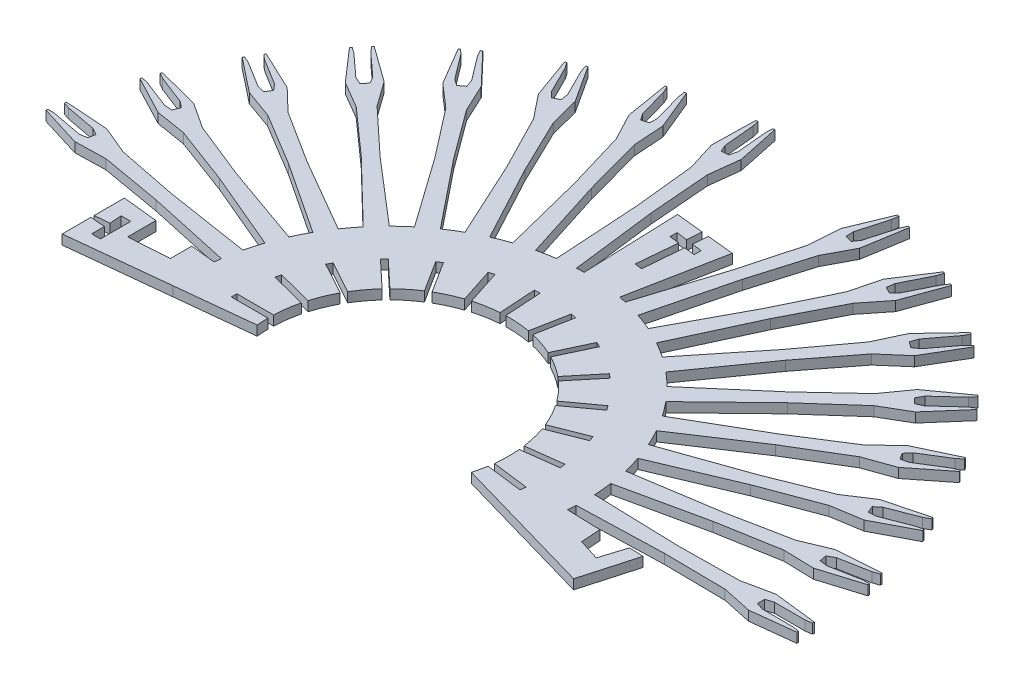
SolidWorks part; units mm, degrees
ref_plane "Front Plane" through (0, 0, 0) normal (0, 0, 1) x (1, 0, 0)
ref_plane "Top Plane" through (0, 0, 0) normal (0, 1, 0) x (1, 0, 0)
ref_plane "Right Plane" through (0, 0, 0) normal (1, 0, 0) x (0, 0, -1)
sketch "Sketch1" plane through (0, 0, 0) normal (0, 1, 0) x (1, 0, 0)
  line L5558 (72.849, 49.9) -> (72.743, 47.748) construction
  line L5559 (72.743, 47.748) -> (72.425, 45.667) construction
  line L5560 (72.425, 45.667) -> (71.896, 43.656) construction
  line L5561 (71.896, 43.656) -> (71.208, 41.716) construction
  line L5562 (71.208, 41.716) -> (70.309, 39.899) construction
  line L5563 (70.309, 39.899) -> (69.286, 38.171) construction
  line L5564 (69.286, 38.171) -> (66.71, 35.048) construction
  line L5565 (66.71, 35.048) -> (63.588, 32.491) construction
  line L5566 (63.588, 32.491) -> (61.877, 31.45) construction
  line L5567 (61.877, 31.45) -> (60.043, 30.551) construction
  line L5568 (60.043, 30.551) -> (58.12, 29.863) construction
  line L5569 (58.12, 29.863) -> (56.109, 29.333) construction
  line L5570 (56.109, 29.333) -> (54.01, 29.016) construction
  line L5571 (54.01, 29.016) -> (51.876, 28.91) construction
  line L5572 (51.876, 28.91) -> (49.724, 29.016) construction
  line L5573 (49.724, 29.016) -> (47.643, 29.333) construction
  line L5574 (47.643, 29.333) -> (45.632, 29.863) construction
  line L5575 (45.632, 29.863) -> (43.692, 30.551) construction
  line L5576 (43.692, 30.551) -> (41.839, 31.45) construction
  line L5577 (41.839, 31.45) -> (40.128, 32.491) construction
  line L5578 (40.128, 32.491) -> (37.006, 35.048) construction
  line L5579 (37.006, 35.048) -> (34.431, 38.171) construction
  line L5580 (34.431, 38.171) -> (33.408, 39.899) construction
  line L5581 (33.408, 39.899) -> (32.508, 41.716) construction
  line L5582 (32.508, 41.716) -> (31.821, 43.656) construction
  line L5583 (31.821, 43.656) -> (31.291, 45.667) construction
  line L5584 (31.291, 45.667) -> (30.974, 47.748) construction
  line L5585 (30.974, 47.748) -> (30.868, 49.9) construction
  line L5586 (30.868, 49.9) -> (30.974, 52.035) construction
  line L5587 (30.974, 52.035) -> (31.291, 54.134) construction
  line L5588 (31.291, 54.134) -> (31.821, 56.145) construction
  line L5589 (31.821, 56.145) -> (32.508, 58.067) construction
  line L5590 (32.508, 58.067) -> (33.408, 59.919) construction
  line L5591 (33.408, 59.919) -> (34.431, 61.648) construction
  line L5592 (34.431, 61.648) -> (37.006, 64.77) construction
  line L5593 (37.006, 64.77) -> (40.128, 67.328) construction
  line L5594 (40.128, 67.328) -> (41.839, 68.368) construction
  line L5595 (41.839, 68.368) -> (43.692, 69.268) construction
  line L5596 (43.692, 69.268) -> (45.632, 69.956) construction
  line L5597 (45.632, 69.956) -> (47.643, 70.485) construction
  line L5598 (47.643, 70.485) -> (49.724, 70.803) construction
  line L5599 (49.724, 70.803) -> (51.876, 70.908) construction
  line L5600 (51.876, 70.908) -> (54.01, 70.803) construction
  line L5601 (54.01, 70.803) -> (56.109, 70.485) construction
  line L5602 (56.109, 70.485) -> (58.12, 69.956) construction
  line L5603 (58.12, 69.956) -> (60.043, 69.268) construction
  line L5604 (60.043, 69.268) -> (61.877, 68.368) construction
  line L5605 (61.877, 68.368) -> (63.588, 67.328) construction
  line L5606 (63.588, 67.328) -> (66.71, 64.77) construction
  line L5607 (66.71, 64.77) -> (69.286, 61.648) construction
  line L5608 (69.286, 61.648) -> (70.309, 59.919) construction
  line L5609 (70.309, 59.919) -> (71.208, 58.067) construction
  line L5610 (71.208, 58.067) -> (71.896, 56.145) construction
  line L5611 (71.896, 56.145) -> (72.425, 54.134) construction
  line L5612 (72.425, 54.134) -> (72.743, 52.035) construction
  line L5613 (72.743, 52.035) -> (72.849, 49.9) construction
  line L5614 (62.054, 49.9) -> (61.842, 47.854) construction
  line L5615 (61.842, 47.854) -> (61.26, 45.932) construction
  line L5616 (61.26, 45.932) -> (60.307, 44.203) construction
  line L5617 (60.307, 44.203) -> (59.055, 42.704) construction
  line L5618 (59.055, 42.704) -> (57.556, 41.451) construction
  line L5619 (57.556, 41.451) -> (55.827, 40.499) construction
  line L5620 (55.827, 40.499) -> (53.922, 39.917) construction
  line L5621 (53.922, 39.917) -> (51.858, 39.705) construction
  line L5622 (51.858, 39.705) -> (49.795, 39.917) construction
  line L5623 (49.795, 39.917) -> (47.89, 40.499) construction
  line L5624 (47.89, 40.499) -> (46.143, 41.451) construction
  line L5625 (46.143, 41.451) -> (44.644, 42.704) construction
  line L5626 (44.644, 42.704) -> (43.392, 44.203) construction
  line L5627 (43.392, 44.203) -> (42.439, 45.932) construction
  line L5628 (42.439, 45.932) -> (41.857, 47.854) construction
  line L5629 (41.857, 47.854) -> (41.645, 49.9) construction
  line L5630 (41.645, 49.9) -> (41.857, 51.964) construction
  line L5631 (41.857, 51.964) -> (42.439, 53.869) construction
  line L5632 (42.439, 53.869) -> (43.392, 55.615) construction
  line L5633 (43.392, 55.615) -> (44.644, 57.115) construction
  line L5634 (44.644, 57.115) -> (46.143, 58.367) construction
  line L5635 (46.143, 58.367) -> (47.89, 59.32) construction
  line L5636 (47.89, 59.32) -> (49.795, 59.902) construction
  line L5637 (49.795, 59.902) -> (51.858, 60.113) construction
  line L5638 (51.858, 60.113) -> (53.922, 59.902) construction
  line L5639 (53.922, 59.902) -> (55.827, 59.32) construction
  line L5640 (55.827, 59.32) -> (57.556, 58.367) construction
  line L5641 (57.556, 58.367) -> (59.055, 57.115) construction
  line L5642 (59.055, 57.115) -> (60.307, 55.615) construction
  line L5643 (60.307, 55.615) -> (61.26, 53.869) construction
  line L5644 (61.26, 53.869) -> (61.842, 51.964) construction
  line L5645 (61.842, 51.964) -> (62.054, 49.9) construction
  line L5646 (30.85, 49.9) -> (51.841, 49.9) construction
  line L5647 (53.675, 70.82) -> (51.841, 49.9) construction
  line L5648 (72.531, 46.249) -> (51.858, 49.9) construction
  line L5649 (72.796, 48.436) -> (51.841, 49.9) construction
  line L5650 (51.488, 70.891) -> (51.841, 49.9) construction
  line L5651 (55.862, 70.52) -> (51.858, 49.9) construction
  line L5652 (30.956, 47.696) -> (51.841, 49.9) construction
  line L5653 (30.956, 52.088) -> (51.841, 49.9) construction
  line L5654 (72.037, 44.115) -> (51.841, 49.9) construction
  line L5655 (62.406, 49.177) -> (67.045, 49.424) construction
  line L5656 (67.345, 50.077) -> (67.469, 50.324) construction
  line L5657 (67.469, 50.324) -> (67.68, 50.377) construction
  line L5658 (67.68, 50.377) -> (67.892, 50.271) construction
  line L5659 (67.892, 50.271) -> (67.945, 50.059) construction
  line L5660 (67.945, 50.059) -> (67.839, 49.848) construction
  line L5661 (67.839, 49.848) -> (67.628, 49.759) construction
  line L5662 (67.628, 49.759) -> (67.416, 49.865) construction
  line L5663 (67.416, 49.865) -> (67.345, 50.077) construction
  line L5664 (69.832, 50.094) -> (69.938, 50.341) construction
  line L5665 (69.938, 50.341) -> (70.168, 50.394) construction
  line L5666 (70.168, 50.394) -> (70.379, 50.288) construction
  line L5667 (70.379, 50.288) -> (70.432, 50.077) construction
  line L5668 (70.432, 50.077) -> (70.326, 49.865) construction
  line L5669 (70.326, 49.865) -> (70.115, 49.777) construction
  line L5670 (70.115, 49.777) -> (69.903, 49.883) construction
  line L5671 (69.903, 49.883) -> (69.832, 50.094) construction
  line L5672 (67.045, 49.424) -> (71.702, 49.477) construction
  line L5673 (71.914, 50.094) -> (71.702, 49.477) construction
  line L5674 (62.389, 50.835) -> (67.045, 50.659) construction
  line L5675 (67.045, 50.659) -> (71.702, 50.712) construction
  line L5676 (71.914, 50.094) -> (71.702, 50.712) construction
  line L5677 (70.132, 50.377) -> (67.645, 50.359) construction
  line L5678 (70.15, 49.777) -> (67.645, 49.742) construction
  line L5679 (57.344, 49.953) -> (51.841, 49.9) construction
  line L5680 (62.353, 51.118) -> (66.887, 52.229) construction
  line L5681 (67.045, 52.917) -> (67.345, 53.252) construction
  line L5682 (67.345, 53.252) -> (67.557, 53.199) construction
  line L5683 (67.557, 53.199) -> (67.663, 52.987) construction
  line L5684 (67.663, 52.987) -> (67.61, 52.776) construction
  line L5685 (67.61, 52.776) -> (67.398, 52.652) construction
  line L5686 (67.398, 52.652) -> (67.187, 52.723) construction
  line L5687 (67.187, 52.723) -> (67.045, 52.917) construction
  line L5688 (69.48, 53.393) -> (69.779, 53.746) construction
  line L5689 (69.779, 53.746) -> (69.991, 53.693) construction
  line L5690 (69.991, 53.693) -> (70.097, 53.481) construction
  line L5691 (70.097, 53.481) -> (70.044, 53.269) construction
  line L5692 (70.044, 53.269) -> (69.832, 53.128) construction
  line L5693 (69.832, 53.128) -> (69.621, 53.217) construction
  line L5694 (69.621, 53.217) -> (69.48, 53.393) construction
  line L5695 (66.887, 52.229) -> (71.455, 53.128) construction
  line L5696 (71.543, 53.763) -> (71.455, 53.128) construction
  line L5697 (62.036, 52.758) -> (66.64, 53.428) construction
  line L5698 (66.64, 53.428) -> (71.208, 54.328) construction
  line L5699 (71.543, 53.781) -> (71.208, 54.328) construction
  line L5700 (69.744, 53.728) -> (67.292, 53.252) construction
  line L5701 (69.85, 53.128) -> (67.416, 52.634) construction
  line L5702 (57.238, 50.959) -> (51.841, 49.9) construction
  line L5703 (61.965, 53.023) -> (66.199, 54.945) construction
  line L5704 (66.234, 55.651) -> (66.446, 56.039) construction
  line L5705 (66.446, 56.039) -> (66.693, 56.021) construction
  line L5706 (66.693, 56.021) -> (66.851, 55.827) construction
  line L5707 (66.851, 55.827) -> (66.64, 55.457) construction
  line L5708 (66.64, 55.457) -> (66.393, 55.492) construction
  line L5709 (66.393, 55.492) -> (66.234, 55.651) construction
  line L5710 (68.545, 56.568) -> (68.756, 56.956) construction
  line L5711 (68.756, 56.956) -> (69.003, 56.938) construction
  line L5712 (69.003, 56.938) -> (69.162, 56.744) construction
  line L5713 (69.162, 56.744) -> (68.95, 56.374) construction
  line L5714 (68.95, 56.374) -> (68.703, 56.409) construction
  line L5715 (68.703, 56.409) -> (68.545, 56.568) construction
  line L5716 (66.199, 54.945) -> (70.52, 56.656) construction
  line L5717 (70.503, 57.309) -> (70.52, 56.656) construction
  line L5718 (61.348, 54.575) -> (65.74, 56.092) construction
  line L5719 (65.74, 56.092) -> (70.079, 57.803) construction
  line L5720 (70.503, 57.309) -> (70.079, 57.803) construction
  line L5721 (68.739, 56.938) -> (66.41, 56.021) construction
  line L5722 (68.968, 56.374) -> (66.64, 55.439) construction
  line L5723 (56.956, 51.929) -> (51.841, 49.9) construction
  line L5724 (61.225, 54.822) -> (65.035, 57.485) construction
  line L5725 (64.946, 58.191) -> (65.07, 58.614) construction
  line L5726 (65.07, 58.614) -> (65.317, 58.632) construction
  line L5727 (65.317, 58.632) -> (65.493, 58.473) construction
  line L5728 (65.493, 58.473) -> (65.528, 58.244) construction
  line L5729 (65.528, 58.244) -> (65.37, 58.05) construction
  line L5730 (65.37, 58.05) -> (64.946, 58.191) construction
  line L5731 (67.045, 59.514) -> (67.169, 59.937) construction
  line L5732 (67.169, 59.937) -> (67.416, 59.955) construction
  line L5733 (67.416, 59.955) -> (67.592, 59.796) construction
  line L5734 (67.592, 59.796) -> (67.628, 59.567) construction
  line L5735 (67.628, 59.567) -> (67.469, 59.373) construction
  line L5736 (67.469, 59.373) -> (67.045, 59.514) construction
  line L5737 (65.035, 57.485) -> (68.968, 59.972) construction
  line L5738 (68.827, 60.607) -> (68.968, 59.972) construction
  line L5739 (60.325, 56.233) -> (64.382, 58.526) construction
  line L5740 (64.382, 58.526) -> (68.315, 61.013) construction
  line L5741 (68.827, 60.607) -> (68.315, 61.013) construction
  line L5742 (67.169, 59.919) -> (65.052, 58.579) construction
  line L5743 (67.486, 59.39) -> (65.37, 58.067) construction
  line L5744 (56.497, 52.828) -> (51.858, 49.9) construction
  line L5745 (60.149, 56.444) -> (63.429, 59.761) construction
  line L5746 (63.2, 60.448) -> (63.147, 60.678) construction
  line L5747 (63.147, 60.678) -> (63.288, 60.889) construction
  line L5748 (63.288, 60.889) -> (63.5, 60.942) construction
  line L5749 (63.5, 60.942) -> (63.712, 60.837) construction
  line L5750 (63.712, 60.837) -> (63.765, 60.607) construction
  line L5751 (63.765, 60.607) -> (63.659, 60.396) construction
  line L5752 (63.659, 60.396) -> (63.412, 60.343) construction
  line L5753 (63.412, 60.343) -> (63.2, 60.448) construction
  line L5754 (65.017, 62.124) -> (64.964, 62.371) construction
  line L5755 (64.964, 62.371) -> (65.105, 62.583) construction
  line L5756 (65.105, 62.583) -> (65.317, 62.636) construction
  line L5757 (65.317, 62.636) -> (65.528, 62.53) construction
  line L5758 (65.528, 62.53) -> (65.581, 62.283) construction
  line L5759 (65.581, 62.283) -> (65.476, 62.071) construction
  line L5760 (65.476, 62.071) -> (65.229, 62.018) construction
  line L5761 (65.229, 62.018) -> (65.017, 62.124) construction
  line L5762 (63.429, 59.761) -> (66.834, 62.936) construction
  line L5763 (66.587, 63.535) -> (66.834, 62.936) construction
  line L5764 (59.02, 57.679) -> (62.583, 60.678) construction
  line L5765 (62.583, 60.678) -> (66.005, 63.835) construction
  line L5766 (66.587, 63.535) -> (66.005, 63.835) construction
  line L5767 (65.07, 62.548) -> (63.235, 60.854) construction
  line L5768 (65.493, 62.089) -> (63.659, 60.396) construction
  line L5769 (55.88, 53.622) -> (51.841, 49.9) construction
  line L5770 (58.808, 57.873) -> (61.419, 61.718) construction
  line L5771 (61.083, 62.353) -> (60.995, 62.583) construction
  line L5772 (60.995, 62.583) -> (61.083, 62.794) construction
  line L5773 (61.083, 62.794) -> (61.295, 62.9) construction
  line L5774 (61.295, 62.9) -> (61.507, 62.83) construction
  line L5775 (61.507, 62.83) -> (61.613, 62.618) construction
  line L5776 (61.613, 62.618) -> (61.524, 62.371) construction
  line L5777 (61.524, 62.371) -> (61.313, 62.301) construction
  line L5778 (61.313, 62.301) -> (61.083, 62.353) construction
  line L5779 (62.565, 64.329) -> (62.477, 64.576) construction
  line L5780 (62.477, 64.576) -> (62.565, 64.788) construction
  line L5781 (62.565, 64.788) -> (62.777, 64.893) construction
  line L5782 (62.777, 64.893) -> (62.988, 64.805) construction
  line L5783 (62.988, 64.805) -> (63.094, 64.594) construction
  line L5784 (63.094, 64.594) -> (63.006, 64.364) construction
  line L5785 (63.006, 64.364) -> (62.794, 64.276) construction
  line L5786 (62.794, 64.276) -> (62.565, 64.329) construction
  line L5787 (61.419, 61.718) -> (64.206, 65.458) construction
  line L5788 (63.835, 66.005) -> (64.206, 65.458) construction
  line L5789 (57.485, 58.861) -> (60.431, 62.459) construction
  line L5790 (60.431, 62.459) -> (63.2, 66.199) construction
  line L5791 (63.835, 66.005) -> (63.2, 66.199) construction
  line L5792 (62.53, 64.752) -> (61.031, 62.759) construction
  line L5793 (63.024, 64.382) -> (61.524, 62.389) construction
  line L5794 (55.122, 54.31) -> (51.858, 49.9) construction
  line L5795 (57.238, 59.002) -> (59.09, 63.271) construction
  line L5796 (58.649, 63.835) -> (58.508, 64.047) construction
  line L5797 (58.508, 64.047) -> (58.561, 64.258) construction
  line L5798 (58.561, 64.258) -> (58.755, 64.417) construction
  line L5799 (58.755, 64.417) -> (58.967, 64.364) construction
  line L5800 (58.967, 64.364) -> (59.126, 64.17) construction
  line L5801 (59.126, 64.17) -> (59.073, 63.941) construction
  line L5802 (59.073, 63.941) -> (58.879, 63.8) construction
  line L5803 (58.879, 63.8) -> (58.649, 63.835) construction
  line L5804 (59.743, 66.058) -> (59.602, 66.269) construction
  line L5805 (59.602, 66.269) -> (59.655, 66.481) construction
  line L5806 (59.655, 66.481) -> (59.849, 66.604) construction
  line L5807 (59.849, 66.604) -> (60.06, 66.587) construction
  line L5808 (60.06, 66.587) -> (60.219, 66.393) construction
  line L5809 (60.219, 66.393) -> (60.166, 66.163) construction
  line L5810 (60.166, 66.163) -> (59.972, 66.022) construction
  line L5811 (59.972, 66.022) -> (59.743, 66.058) construction
  line L5812 (59.09, 63.271) -> (61.136, 67.451) construction
  line L5813 (60.695, 67.927) -> (61.136, 67.451) construction
  line L5814 (55.739, 59.743) -> (57.979, 63.818) construction
  line L5815 (57.979, 63.818) -> (60.025, 67.998) construction
  line L5816 (60.678, 67.927) -> (60.025, 67.998) construction
  line L5817 (59.619, 66.463) -> (58.526, 64.223) construction
  line L5818 (60.184, 66.181) -> (59.073, 63.941) construction
  line L5819 (54.257, 54.822) -> (51.841, 49.9) construction
  line L5820 (55.457, 59.849) -> (56.497, 64.382) construction
  line L5821 (55.951, 64.841) -> (55.792, 64.999) construction
  line L5822 (55.792, 64.999) -> (55.792, 65.246) construction
  line L5823 (55.792, 65.246) -> (55.951, 65.423) construction
  line L5824 (55.951, 65.423) -> (56.18, 65.423) construction
  line L5825 (56.18, 65.423) -> (56.339, 65.264) construction
  line L5826 (56.339, 65.264) -> (56.339, 65.035) construction
  line L5827 (56.339, 65.035) -> (56.18, 64.876) construction
  line L5828 (56.18, 64.876) -> (55.951, 64.841) construction
  line L5829 (56.603, 67.239) -> (56.444, 67.398) construction
  line L5830 (56.444, 67.398) -> (56.444, 67.628) construction
  line L5831 (56.444, 67.628) -> (56.603, 67.822) construction
  line L5832 (56.603, 67.822) -> (56.85, 67.822) construction
  line L5833 (56.85, 67.822) -> (57.009, 67.663) construction
  line L5834 (57.009, 67.663) -> (57.009, 67.416) construction
  line L5835 (57.009, 67.416) -> (56.85, 67.257) construction
  line L5836 (56.85, 67.257) -> (56.603, 67.239) construction
  line L5837 (56.497, 64.382) -> (57.732, 68.88) construction
  line L5838 (57.203, 69.25) -> (57.732, 68.88) construction
  line L5839 (53.852, 60.29) -> (55.298, 64.717) construction
  line L5840 (55.298, 64.717) -> (56.533, 69.197) construction
  line L5841 (57.185, 69.25) -> (56.533, 69.197) construction
  line L5842 (56.427, 67.61) -> (55.757, 65.211) construction
  line L5843 (57.009, 67.451) -> (56.356, 65.035) construction
  line L5844 (53.305, 55.192) -> (51.841, 49.9) construction
  line L5845 (51.664, 60.484) -> (50.994, 65.088) construction
  line L5846 (50.324, 65.317) -> (50.112, 65.423) construction
  line L5847 (50.112, 65.423) -> (50.024, 65.634) construction
  line L5848 (50.024, 65.634) -> (50.112, 65.846) construction
  line L5849 (50.112, 65.846) -> (50.324, 65.952) construction
  line L5850 (50.324, 65.952) -> (50.553, 65.846) construction
  line L5851 (50.553, 65.846) -> (50.641, 65.634) construction
  line L5852 (50.641, 65.634) -> (50.553, 65.423) construction
  line L5853 (50.553, 65.423) -> (50.324, 65.317) construction
  line L5854 (50.077, 67.786) -> (49.865, 67.892) construction
  line L5855 (49.865, 67.892) -> (49.795, 68.104) construction
  line L5856 (49.795, 68.104) -> (49.865, 68.315) construction
  line L5857 (49.865, 68.315) -> (50.077, 68.421) construction
  line L5858 (50.077, 68.421) -> (50.324, 68.315) construction
  line L5859 (50.324, 68.315) -> (50.394, 68.104) construction
  line L5860 (50.394, 68.104) -> (50.324, 67.892) construction
  line L5861 (50.324, 67.892) -> (50.077, 67.786) construction
  line L5862 (50.994, 65.088) -> (50.535, 69.727) construction
  line L5863 (49.918, 69.885) -> (50.535, 69.727) construction
  line L5864 (50.006, 60.325) -> (49.759, 64.964) construction
  line L5865 (49.759, 64.964) -> (49.318, 69.603) construction
  line L5866 (49.9, 69.885) -> (49.318, 69.603) construction
  line L5867 (49.777, 68.068) -> (50.024, 65.599) construction
  line L5868 (50.377, 68.139) -> (50.624, 65.652) construction
  line L5869 (51.312, 55.368) -> (51.858, 49.9) construction
  line L5870 (49.724, 60.272) -> (48.225, 64.664) construction
  line L5871 (47.519, 64.788) -> (47.308, 64.841) construction
  line L5872 (47.308, 64.841) -> (47.184, 65.052) construction
  line L5873 (47.184, 65.052) -> (47.237, 65.264) construction
  line L5874 (47.237, 65.264) -> (47.413, 65.387) construction
  line L5875 (47.413, 65.387) -> (47.66, 65.334) construction
  line L5876 (47.66, 65.334) -> (47.784, 65.158) construction
  line L5877 (47.784, 65.158) -> (47.731, 64.946) construction
  line L5878 (47.731, 64.946) -> (47.519, 64.788) construction
  line L5879 (46.831, 67.169) -> (46.62, 67.222) construction
  line L5880 (46.62, 67.222) -> (46.496, 67.433) construction
  line L5881 (46.496, 67.433) -> (46.549, 67.645) construction
  line L5882 (46.549, 67.645) -> (46.725, 67.769) construction
  line L5883 (46.725, 67.769) -> (46.972, 67.716) construction
  line L5884 (46.972, 67.716) -> (47.096, 67.539) construction
  line L5885 (47.096, 67.539) -> (47.043, 67.328) construction
  line L5886 (47.043, 67.328) -> (46.831, 67.169) construction
  line L5887 (48.225, 64.664) -> (46.937, 69.144) construction
  line L5888 (46.284, 69.18) -> (46.937, 69.144) construction
  line L5889 (48.119, 59.796) -> (47.043, 64.329) construction
  line L5890 (47.043, 64.329) -> (45.738, 68.809) construction
  line L5891 (46.267, 69.18) -> (45.738, 68.792) construction
  line L5892 (46.478, 67.381) -> (47.166, 64.982) construction
  line L5893 (47.061, 67.557) -> (47.766, 65.158) construction
  line L5894 (50.324, 55.174) -> (51.841, 49.9) construction
  line L5895 (47.854, 59.708) -> (45.579, 63.747) construction
  line L5896 (44.873, 63.729) -> (44.662, 63.765) construction
  line L5897 (44.662, 63.765) -> (44.503, 63.923) construction
  line L5898 (44.503, 63.923) -> (44.503, 64.153) construction
  line L5899 (44.503, 64.153) -> (44.662, 64.311) construction
  line L5900 (44.662, 64.311) -> (44.891, 64.311) construction
  line L5901 (44.891, 64.311) -> (45.05, 64.135) construction
  line L5902 (45.05, 64.135) -> (45.05, 63.923) construction
  line L5903 (45.05, 63.923) -> (44.873, 63.729) construction
  line L5904 (43.762, 65.952) -> (43.55, 65.969) construction
  line L5905 (43.55, 65.969) -> (43.356, 66.128) construction
  line L5906 (43.356, 66.128) -> (43.392, 66.375) construction
  line L5907 (43.392, 66.375) -> (43.55, 66.534) construction
  line L5908 (43.55, 66.534) -> (43.78, 66.534) construction
  line L5909 (43.78, 66.534) -> (43.938, 66.34) construction
  line L5910 (43.938, 66.34) -> (43.938, 66.128) construction
  line L5911 (43.938, 66.128) -> (43.762, 65.952) construction
  line L5912 (45.579, 63.747) -> (43.498, 67.91) construction
  line L5913 (42.845, 67.839) -> (43.498, 67.91) construction
  line L5914 (46.373, 58.949) -> (44.485, 63.2) construction
  line L5915 (44.485, 63.2) -> (42.386, 67.363) construction
  line L5916 (42.827, 67.839) -> (42.386, 67.363) construction
  line L5917 (43.374, 66.111) -> (44.485, 63.87) construction
  line L5918 (43.921, 66.393) -> (45.032, 64.153) construction
  line L5919 (49.389, 54.804) -> (51.841, 49.9) construction
  line L5920 (46.126, 58.808) -> (43.145, 62.371) construction
  line L5921 (42.457, 62.23) -> (42.245, 62.195) construction
  line L5922 (42.245, 62.195) -> (42.051, 62.336) construction
  line L5923 (42.051, 62.336) -> (41.998, 62.565) construction
  line L5924 (41.998, 62.565) -> (42.139, 62.759) construction
  line L5925 (42.139, 62.759) -> (42.369, 62.777) construction
  line L5926 (42.369, 62.777) -> (42.563, 62.653) construction
  line L5927 (42.563, 62.653) -> (42.58, 62.442) construction
  line L5928 (42.58, 62.442) -> (42.457, 62.23) construction
  line L5929 (40.958, 64.188) -> (40.746, 64.17) construction
  line L5930 (40.746, 64.17) -> (40.552, 64.294) construction
  line L5931 (40.552, 64.294) -> (40.499, 64.541) construction
  line L5932 (40.499, 64.541) -> (40.64, 64.717) construction
  line L5933 (40.64, 64.717) -> (40.869, 64.752) construction
  line L5934 (40.869, 64.752) -> (41.063, 64.611) construction
  line L5935 (41.063, 64.611) -> (41.081, 64.4) construction
  line L5936 (41.081, 64.4) -> (40.958, 64.188) construction
  line L5937 (43.145, 62.371) -> (40.323, 66.075) construction
  line L5938 (39.705, 65.881) -> (40.323, 66.075) construction
  line L5939 (44.803, 57.803) -> (42.157, 61.63) construction
  line L5940 (42.157, 61.63) -> (39.352, 65.334) construction
  line L5941 (39.705, 65.881) -> (39.352, 65.334) construction
  line L5942 (40.534, 64.276) -> (42.051, 62.301) construction
  line L5943 (41.028, 64.647) -> (42.545, 62.671) construction
  line L5944 (48.525, 54.275) -> (51.858, 49.9) construction
  line L5945 (44.591, 57.609) -> (41.01, 60.572) construction
  line L5946 (40.358, 60.29) -> (40.146, 60.219) construction
  line L5947 (40.146, 60.219) -> (39.934, 60.325) construction
  line L5948 (39.934, 60.325) -> (39.846, 60.537) construction
  line L5949 (39.846, 60.537) -> (39.952, 60.748) construction
  line L5950 (39.952, 60.748) -> (40.164, 60.819) construction
  line L5951 (40.164, 60.819) -> (40.375, 60.748) construction
  line L5952 (40.375, 60.748) -> (40.464, 60.537) construction
  line L5953 (40.464, 60.537) -> (40.358, 60.29) construction
  line L5954 (38.523, 61.965) -> (38.312, 61.877) construction
  line L5955 (38.312, 61.877) -> (38.1, 61.983) construction
  line L5956 (38.1, 61.983) -> (38.012, 62.195) construction
  line L5957 (38.012, 62.195) -> (38.118, 62.406) construction
  line L5958 (38.118, 62.406) -> (38.329, 62.495) construction
  line L5959 (38.329, 62.495) -> (38.541, 62.406) construction
  line L5960 (38.541, 62.406) -> (38.629, 62.195) construction
  line L5961 (38.629, 62.195) -> (38.523, 61.965) construction
  line L5962 (41.01, 60.572) -> (37.553, 63.694) construction
  line L5963 (36.989, 63.394) -> (37.553, 63.694) construction
  line L5964 (43.48, 56.374) -> (40.181, 59.655) construction
  line L5965 (40.181, 59.655) -> (36.724, 62.777) construction
  line L5966 (36.971, 63.377) -> (36.724, 62.777) construction
  line L5967 (38.1, 61.965) -> (39.952, 60.29) construction
  line L5968 (38.506, 62.424) -> (40.358, 60.748) construction
  line L5969 (47.784, 53.587) -> (51.841, 49.9) construction
  line L5970 (43.303, 56.145) -> (39.247, 58.402) construction
  line L5971 (38.647, 58.014) -> (38.453, 57.908) construction
  line L5972 (38.453, 57.908) -> (38.223, 57.961) construction
  line L5973 (38.223, 57.961) -> (38.118, 58.173) construction
  line L5974 (38.118, 58.173) -> (38.171, 58.385) construction
  line L5975 (38.171, 58.385) -> (38.594, 58.455) construction
  line L5976 (38.594, 58.455) -> (38.7, 58.244) construction
  line L5977 (38.7, 58.244) -> (38.647, 58.014) construction
  line L5978 (36.53, 59.32) -> (36.354, 59.214) construction
  line L5979 (36.354, 59.214) -> (36.107, 59.267) construction
  line L5980 (36.107, 59.267) -> (36.001, 59.478) construction
  line L5981 (36.001, 59.478) -> (36.054, 59.69) construction
  line L5982 (36.054, 59.69) -> (36.477, 59.761) construction
  line L5983 (36.477, 59.761) -> (36.583, 59.549) construction
  line L5984 (36.583, 59.549) -> (36.53, 59.32) construction
  line L5985 (39.247, 58.402) -> (35.278, 60.854) construction
  line L5986 (34.766, 60.448) -> (35.278, 60.837) construction
  line L5987 (42.439, 54.733) -> (38.594, 57.344) construction
  line L5988 (38.594, 57.344) -> (34.625, 59.796) construction
  line L5989 (34.766, 60.431) -> (34.625, 59.796) construction
  line L5990 (36.124, 59.249) -> (38.241, 57.926) construction
  line L5991 (36.442, 59.761) -> (38.559, 58.455) construction
  line L5992 (47.184, 52.776) -> (51.841, 49.9) construction
  line L5993 (42.316, 54.469) -> (37.888, 55.951) construction
  line L5994 (37.377, 55.457) -> (37.218, 55.316) construction
  line L5995 (37.218, 55.316) -> (36.989, 55.316) construction
  line L5996 (36.989, 55.316) -> (36.83, 55.51) construction
  line L5997 (36.83, 55.51) -> (36.848, 55.739) construction
  line L5998 (36.848, 55.739) -> (37.006, 55.898) construction
  line L5999 (37.006, 55.898) -> (37.253, 55.88) construction
  line L6000 (37.253, 55.88) -> (37.412, 55.686) construction
  line L6001 (37.412, 55.686) -> (37.377, 55.457) construction
  line L6002 (35.066, 56.356) -> (34.907, 56.215) construction
  line L6003 (34.907, 56.215) -> (34.678, 56.215) construction
  line L6004 (34.678, 56.215) -> (34.519, 56.409) construction
  line L6005 (34.519, 56.409) -> (34.537, 56.638) construction
  line L6006 (34.537, 56.638) -> (34.696, 56.797) construction
  line L6007 (34.696, 56.797) -> (34.943, 56.78) construction
  line L6008 (34.943, 56.78) -> (35.101, 56.586) construction
  line L6009 (35.101, 56.586) -> (35.066, 56.356) construction
  line L6010 (37.888, 55.951) -> (33.549, 57.626) construction
  line L6011 (33.126, 57.132) -> (33.549, 57.626) construction
  line L6012 (41.716, 52.917) -> (37.447, 54.804) construction
  line L6013 (37.447, 54.804) -> (33.108, 56.48) construction
  line L6014 (33.126, 57.132) -> (33.108, 56.48) construction
  line L6015 (34.678, 56.198) -> (37.006, 55.298) construction
  line L6016 (34.89, 56.78) -> (37.218, 55.88) construction
  line L6017 (46.725, 51.876) -> (51.858, 49.9) construction
  line L6018 (41.628, 52.652) -> (37.024, 53.287) construction
  line L6019 (36.601, 52.705) -> (36.477, 52.529) construction
  line L6020 (36.477, 52.529) -> (36.23, 52.493) construction
  line L6021 (36.23, 52.493) -> (36.054, 52.652) construction
  line L6022 (36.054, 52.652) -> (36.019, 52.899) construction
  line L6023 (36.019, 52.899) -> (36.389, 53.111) construction
  line L6024 (36.389, 53.111) -> (36.583, 52.952) construction
  line L6025 (36.583, 52.952) -> (36.601, 52.705) construction
  line L6026 (34.167, 53.164) -> (34.043, 52.987) construction
  line L6027 (34.043, 52.987) -> (33.796, 52.952) construction
  line L6028 (33.796, 52.952) -> (33.62, 53.111) construction
  line L6029 (33.62, 53.111) -> (33.584, 53.358) construction
  line L6030 (33.584, 53.358) -> (33.955, 53.569) construction
  line L6031 (33.955, 53.569) -> (34.149, 53.411) construction
  line L6032 (34.149, 53.411) -> (34.167, 53.164) construction
  line L6033 (37.024, 53.287) -> (32.438, 54.134) construction
  line L6034 (32.12, 53.587) -> (32.438, 54.134) construction
  line L6035 (41.328, 51.012) -> (36.795, 52.07) construction
  line L6036 (36.795, 52.07) -> (32.226, 52.934) construction
  line L6037 (32.12, 53.569) -> (32.226, 52.934) construction
  line L6038 (33.814, 52.952) -> (36.266, 52.493) construction
  line L6039 (33.92, 53.552) -> (36.371, 53.093) construction
  line L6040 (46.461, 50.906) -> (51.858, 49.9) construction
  line L6041 (57.856, 49.9) -> (57.714, 48.683) construction
  line L6042 (57.714, 48.683) -> (57.379, 47.572) construction
  line L6043 (57.379, 47.572) -> (56.815, 46.567) construction
  line L6044 (56.815, 46.567) -> (56.109, 45.667) construction
  line L6045 (56.109, 45.667) -> (55.21, 44.944) construction
  line L6046 (55.21, 44.944) -> (54.204, 44.397) construction
  line L6047 (54.204, 44.397) -> (53.093, 44.044) construction
  line L6048 (53.093, 44.044) -> (51.876, 43.921) construction
  line L6049 (51.876, 43.921) -> (50.659, 44.044) construction
  line L6050 (50.659, 44.044) -> (49.512, 44.397) construction
  line L6051 (49.512, 44.397) -> (48.507, 44.944) construction
  line L6052 (48.507, 44.944) -> (47.607, 45.667) construction
  line L6053 (47.607, 45.667) -> (46.902, 46.567) construction
  line L6054 (46.902, 46.567) -> (46.337, 47.572) construction
  line L6055 (46.337, 47.572) -> (46.002, 48.683) construction
  line L6056 (46.002, 48.683) -> (45.861, 49.9) construction
  line L6057 (45.861, 49.9) -> (46.002, 51.118) construction
  line L6058 (46.002, 51.118) -> (46.337, 52.246) construction
  line L6059 (46.337, 52.246) -> (46.902, 53.252) construction
  line L6060 (46.902, 53.252) -> (47.607, 54.151) construction
  line L6061 (47.607, 54.151) -> (48.507, 54.875) construction
  line L6062 (48.507, 54.875) -> (49.512, 55.421) construction
  line L6063 (49.512, 55.421) -> (50.659, 55.774) construction
  line L6064 (50.659, 55.774) -> (51.876, 55.898) construction
  line L6065 (51.876, 55.898) -> (53.093, 55.774) construction
  line L6066 (53.093, 55.774) -> (54.204, 55.421) construction
  line L6067 (54.204, 55.421) -> (55.21, 54.875) construction
  line L6068 (55.21, 54.875) -> (56.109, 54.151) construction
  line L6069 (56.109, 54.151) -> (56.815, 53.252) construction
  line L6070 (56.815, 53.252) -> (57.379, 52.246) construction
  line L6071 (57.379, 52.246) -> (57.714, 51.118) construction
  line L6072 (57.714, 51.118) -> (57.856, 49.9) construction
sketch "Sketch2" plane through (0, 0, 0) normal (0, 1, 0) x (1, 0, 0)
  line L0 (41.7366, 50.9583) -> (36.5552, 51.5014)
  line L1 (51.841, 49.9) -> (53.163, 64.9033) construction
  line L2 (30.956, 52.088) -> (51.841, 49.9) construction
  line L3 (36.5552, 51.5014) -> (36.5552, 48.2869)
  line L4 (30.956, 47.696) -> (51.841, 49.9) construction
  line L5 (36.5552, 48.2869) -> (41.7327, 48.8337)
  line L7 (61.6124, 47.1011) -> (66.5007, 45.7008)
  line L8 (72.037, 44.115) -> (51.841, 49.9) construction
  line L9 (66.5007, 45.7008) -> (67.012, 48.8401)
  line L10 (72.796, 48.436) -> (51.841, 49.9) construction
  line L11 (67.012, 48.8401) -> (61.9609, 49.0012)
  line L12 (62.054, 49.9) -> (61.842, 47.854) construction
  line L13 (51.765, 60.0594) -> (51.586, 65.0642)
  line L14 (51.488, 70.891) -> (51.841, 49.9) construction
  line L15 (51.586, 65.0642) -> (54.7401, 64.7424)
  line L16 (55.862, 70.52) -> (51.858, 49.9) construction
  line L17 (54.7401, 64.7424) -> (53.794, 59.8702)
  circle A0 centre (51.841, 49.9) radius 6.2002
  arc A1 (61.9609, 49.0012) -> (53.794, 59.8702) centre (51.841, 49.9) ccw
  arc A2 (41.7375, 50.967) -> (41.7366, 50.9583) centre (51.841, 49.9) ccw
  arc A3 (41.7327, 48.8337) -> (41.7338, 48.8238) centre (51.841, 49.9) ccw
  arc A4 (41.7338, 48.8238) -> (61.6124, 47.1011) centre (51.841, 49.9) ccw
  arc A5 (51.765, 60.0594) -> (41.7375, 50.967) centre (51.841, 49.9) ccw
extrude "Boss-Extrude1" add sketch "Sketch2" along normal blind 0.5
sketch "Sketch3" plane through (0, 0, 0) normal (0, 1, 0) x (1, 0, 0)
  line L0 (34.2118, 50.4323) -> (32.9093, 50.6404) construction
  line L1 (30.85, 49.9) -> (51.841, 49.9) construction
  line L2 (41.7282, 50.4911) -> (37.2554, 50.3818) construction
  line L3 (32.9093, 50.6404) -> (30.8099, 50.6404) construction
  line L4 (30.8099, 50.6404) -> (30.3951, 50.6098) construction
  line L5 (30.3951, 50.6098) -> (30.1967, 50.3818) construction
  line L6 (32.1942, 50.0581) -> (31.3331, 50.0581) construction
  line L7 (37.2554, 50.3818) -> (34.2118, 50.4323) construction
  line L8 (31.0996, 50.116) -> (31.0522, 50.1661) construction
  line L9 (30.7793, 50.1661) -> (31.0522, 50.1661) construction
  line L10 (32.1963, 49.7413) -> (31.4424, 49.7413) construction
  line L11 (41.7282, 50.4911) -> (41.7282, 49.4512) construction
  line L12 (31.194, 49.6753) -> (31.1199, 49.6329) construction
  line L13 (30.7793, 50.1661) -> (30.7516, 50.116) construction
  line L14 (30.7516, 50.116) -> (30.1967, 50.1553) construction
  line L15 (30.7788, 49.6329) -> (31.1199, 49.6329) construction
  line L16 (30.1967, 50.1553) -> (30.1967, 50.3818) construction
  line L17 (30.3951, 49.2413) -> (30.1967, 49.4512) construction
  line L18 (30.8191, 49.1966) -> (30.3951, 49.2413) construction
  line L19 (32.6688, 49.1966) -> (30.8191, 49.1966) construction
  line L20 (41.7282, 49.4512) -> (37.2554, 49.5186) construction
  line L21 (34.213, 49.341) -> (32.6688, 49.1966) construction
  line L22 (30.7788, 49.6329) -> (30.7516, 49.685) construction
  line L23 (30.7516, 49.685) -> (30.1967, 49.6405) construction
  line L24 (30.1967, 49.6405) -> (30.1967, 49.4512) construction
  line L25 (37.2554, 49.5186) -> (34.213, 49.341) construction
  line L26 (51.841, 49.9) -> (28.9127, 49.9) construction
  line L27 (32.2385, 50.21) -> (30.6564, 50.21)
  line L28 (30.3129, 50.2585) -> (30.3129, 50.3538)
  line L29 (30.3129, 50.3538) -> (32.5485, 50.6098)
  line L30 (32.5485, 50.6098) -> (34.0857, 50.2819)
  line L31 (34.0857, 50.2819) -> (37.2554, 50.2437)
  line L32 (37.2554, 50.2437) -> (41.8575, 50.3818)
  line L33 (41.8575, 50.3818) -> (41.8575, 49.4182)
  line L34 (32.2385, 50.21) -> (32.6151, 50.0861)
  line L35 (32.6151, 50.0861) -> (32.6151, 49.7139)
  line L36 (30.6564, 50.21) -> (30.3129, 50.2585)
  line L37 (37.2554, 49.5563) -> (41.8575, 49.4182)
  line L38 (34.0857, 49.5181) -> (37.2554, 49.5563)
  line L39 (32.5485, 49.1902) -> (34.0857, 49.5181)
  line L40 (30.3129, 49.4462) -> (32.5485, 49.1902)
  line L41 (30.6564, 49.59) -> (30.3129, 49.5415)
  line L42 (30.3129, 49.5415) -> (30.3129, 49.4462)
  line L43 (32.2385, 49.59) -> (30.6564, 49.59)
  line L44 (32.2385, 49.59) -> (32.6151, 49.7139)
  circle A0 centre (32.2385, 49.7358) radius 0.1651 construction
  circle A1 centre (30.7793, 50.1661) radius 0.1651 construction
  circle A2 centre (32.2385, 49.9) radius 0.31 construction
  circle A3 centre (32.2385, 50.0642) radius 0.1651 construction
  circle A4 centre (35.387, 50.2437) radius 0.1651 construction
  arc A5 (31.3331, 50.0581) -> (31.0996, 50.116) centre (31.3331, 50.5581) cw construction
  arc A6 (32.1963, 49.7413) -> (32.1942, 50.0581) centre (32.2385, 49.9) ccw construction
  arc A7 (31.4424, 49.7413) -> (31.194, 49.6753) centre (31.4424, 49.2413) ccw construction
  circle A8 centre (32.2385, 50.3818) radius 0.1651 construction
  point P21 (41.7282, 49.9)
  point P54 (41.7282, 49.9)
  point P60 (41.8575, 49.9)
  point P68 (32.6151, 49.9)
extrude "Boss-Extrude2" add sketch "Sketch3" along normal blind 0.5
sketch "Sketch5" plane through (0, 0, 0) normal (0, 1, 0) x (1, 0, 0)
  line L0 (51.841, 49.9) -> (51.841, 47.986)
  line L1 (30.85, 49.9) -> (51.841, 49.9) construction
  line L2 (51.841, 49.9) -> (47.5187, 49.9)
  line L4 (47.5187, 49.9) -> (51.841, 47.986)
extrude "Boss-Extrude3" add sketch "Sketch5" along normal blind 0.5 separate body
pattern_circular "CirPattern1" count 18 over 180 about axis through (51.841, 0.5, -49.9) along (0, -1, 0) of "Boss-Extrude2"
sketch "Sketch8" plane through (0, 0, 0) normal (0, 1, 0) x (1, 0, 0)
  line L0 (36.5552, 48.2869) -> (27.9956, 47.1697)
  line L1 (27.9956, 47.1697) -> (27.9956, 52.8907)
  line L2 (27.9956, 52.8907) -> (36.5552, 51.5014)
  line L3 (36.5552, 51.5014) -> (36.5552, 48.754)
  line L5 (36.5552, 48.754) -> (36.5552, 48.2869)
  line L6 (51.6556, 72.5266) -> (51.586, 65.0642)
  line L7 (51.586, 65.0642) -> (54.7401, 64.7424)
  line L8 (54.7401, 64.7424) -> (56.407, 72.5266)
  line L9 (56.407, 72.5266) -> (51.6556, 72.5266)
  line L10 (47.955, 51.5014) -> (46.9983, 48.798)
  line L11 (46.9983, 48.798) -> (52.8392, 46.1614)
  line L12 (52.8392, 46.1614) -> (54.7401, 51.7191)
  line L13 (56.497, 52.828) -> (51.858, 49.9) construction
  line L14 (54.7401, 51.7191) -> (47.955, 51.5014)
extrude "Cut-Extrude4" cut sketch "Sketch8" against normal blind 0.5 and the other way through all
sketch "Sketch9" plane through (0, 0, 0) normal (0, 1, 0) x (1, 0, 0)
  line L0 (36.5552, 48.2869) -> (47.0091, 49.3901)
  line L1 (51.841, 49.9) -> (66.5007, 45.7008)
  line L2 (66.5007, 45.7008) -> (51.841, 34.8579)
  line L3 (51.841, 34.8579) -> (36.5552, 48.2869)
  line L4 (47.0091, 49.3901) -> (47.588, 50.4909)
  line L5 (47.588, 50.4909) -> (51.841, 49.9)
extrude "Cut-Extrude6" cut sketch "Sketch9" against normal blind 0.5 and the other way through all
sketch "Sketch12" plane through (0, 0, 0) normal (0, 1, 0) x (1, 0, 0)
  line L0 (36.5552, 51.5014) -> (38.3774, 51.5014)
  line L1 (38.3774, 51.5014) -> (38.3774, 49.8464)
  line L2 (38.3774, 49.8464) -> (40.4501, 49.9851)
  line L3 (40.4501, 49.9851) -> (40.4501, 51.1692)
  line L4 (40.4501, 51.1692) -> (37.3172, 51.7206)
  line L5 (37.3172, 51.7206) -> (36.5552, 51.5014)
  line L6 (66.0368, 49.0067) -> (65.0952, 45.6712)
  line L7 (53.0825, 66.1281) -> (52.9481, 64.1718)
  line L8 (67.012, 48.8401) -> (61.9609, 49.0012) construction
  line L9 (65.2739, 48.8955) -> (64.8588, 47.5883)
  line L10 (64.8588, 47.5883) -> (63.7611, 47.9369)
  line L11 (63.7611, 47.9369) -> (63.678, 49.0649)
  line L12 (63.678, 49.0649) -> (65.5048, 49.0067)
  line L13 (65.5048, 49.0067) -> (65.2739, 48.8955)
  line L14 (65.0952, 45.6712) -> (66.9581, 45.1452)
  line L15 (35.4312, 49.8586) -> (37.3125, 49.9972)
  line L16 (37.3125, 49.9972) -> (37.2663, 50.6247)
  line L17 (37.2663, 50.6247) -> (37.7661, 50.6247)
  line L18 (37.7661, 50.6247) -> (37.7661, 49.0512)
  line L19 (37.7661, 49.0512) -> (37.3125, 49.0512)
  line L20 (37.3125, 49.0512) -> (37.3125, 49.7158)
  line L21 (37.3125, 49.7158) -> (35.4312, 49.8586)
  line L22 (66.9581, 45.1452) -> (67.4623, 48.8914)
  line L23 (67.4623, 48.8914) -> (66.0368, 49.0067)
  line L24 (52.9481, 64.1718) -> (52.3858, 64.243)
  line L25 (52.3858, 64.243) -> (52.3858, 63.8789)
  line L26 (52.3858, 63.8789) -> (52.896, 63.8143)
  line L27 (53.8144, 63.698) -> (53.8144, 64.0546)
  line L28 (53.8144, 64.0546) -> (53.3003, 64.1253)
  line L29 (53.3003, 64.1253) -> (53.4738, 66.0149)
  line L30 (52.896, 63.8143) -> (52.7084, 61.7546)
  line L31 (53.2624, 63.7552) -> (53.8144, 63.698)
  line L32 (52.7084, 61.7546) -> (53.0877, 61.7007)
  line L33 (53.0877, 61.7007) -> (53.2624, 63.7552)
  line L34 (51.841, 49.9) -> (53.5625, 69.0822) construction
  line L35 (53.4738, 66.0149) -> (53.0825, 66.1281)
  circle A0 centre (0, 0) radius 0.1651 construction
  circle A1 centre (52.4536, 66.1109) radius 0.1651 construction
extrude "Cut-Extrude13" cut sketch "Sketch12" along normal blind 10
sketch "Sketch13" plane through (0, 0, 0) normal (0, 1, 0) x (1, 0, 0)
  line L0 (49.3736, 50.47) -> (43.9869, 51.853)
  line L1 (49.3092, 49.8384) -> (43.7478, 49.8384)
  line L2 (49.3092, 49.8384) -> (49.3092, 50.1245)
  line L3 (49.3092, 50.1245) -> (43.7478, 50.1245)
  line L4 (43.7478, 49.8384) -> (43.7478, 50.1245)
  line L5 (49.3736, 50.47) -> (49.4447, 50.7471)
  line L6 (49.4447, 50.7471) -> (44.058, 52.1302)
  line L7 (43.9869, 51.853) -> (44.058, 52.1302)
  line L8 (49.593, 51.0657) -> (44.7195, 53.7449)
  line L9 (49.593, 51.0657) -> (49.7308, 51.3164)
  line L10 (49.7308, 51.3164) -> (44.8573, 53.9956)
  line L11 (44.7195, 53.7449) -> (44.8573, 53.9956)
  line L12 (49.9537, 51.5881) -> (45.8996, 55.3952)
  line L13 (49.9537, 51.5881) -> (50.1496, 51.7967)
  line L14 (50.1496, 51.7967) -> (46.0955, 55.6037)
  line L15 (45.8996, 55.3952) -> (46.0955, 55.6037)
  line L16 (50.433, 52.0044) -> (47.453, 56.7001)
  line L17 (50.433, 52.0044) -> (50.6746, 52.1577)
  line L18 (50.6746, 52.1577) -> (47.6946, 56.8534)
  line L19 (47.453, 56.7001) -> (47.6946, 56.8534)
  line L20 (51.0007, 52.2885) -> (49.2822, 57.5777)
  line L21 (51.0007, 52.2885) -> (51.2728, 52.3769)
  line L22 (51.2728, 52.3769) -> (49.5543, 57.6661)
  line L23 (49.2822, 57.5777) -> (49.5543, 57.6661)
  line L24 (51.6213, 52.4224) -> (51.2721, 57.9729)
  line L25 (51.6213, 52.4224) -> (51.9068, 52.4404)
  line L26 (51.9068, 52.4404) -> (51.5576, 57.9908)
  line L27 (51.2721, 57.9729) -> (51.5576, 57.9908)
  line L28 (52.2557, 52.3978) -> (53.2978, 57.8607)
  line L29 (52.2557, 52.3978) -> (52.5367, 52.3442)
  line L30 (52.5367, 52.3442) -> (53.5788, 57.8071)
  line L31 (53.2978, 57.8607) -> (53.5788, 57.8071)
  line L32 (52.864, 52.2162) -> (55.2319, 57.2483)
  line L33 (52.864, 52.2162) -> (53.1229, 52.0944)
  line L34 (53.1229, 52.0944) -> (55.4908, 57.1265)
  line L35 (55.2319, 57.2483) -> (55.4908, 57.1265)
  line L36 (53.408, 51.889) -> (56.953, 56.1742)
  line L37 (53.408, 51.889) -> (53.6285, 51.7067)
  line L38 (53.6285, 51.7067) -> (57.1735, 55.9918)
  line L39 (56.953, 56.1742) -> (57.1735, 55.9918)
  line L40 (53.8536, 51.4369) -> (58.3529, 54.7058)
  line L41 (53.8536, 51.4369) -> (54.0218, 51.2054)
  line L42 (54.0218, 51.2054) -> (58.5211, 54.4743)
  line L43 (58.3529, 54.7058) -> (58.5211, 54.4743)
  line L44 (54.1728, 50.8881) -> (59.3437, 52.9354)
  line L45 (54.1728, 50.8881) -> (54.2781, 50.622)
  line L46 (54.2781, 50.622) -> (59.449, 52.6693)
  line L47 (59.3437, 52.9354) -> (59.449, 52.6693)
  line L48 (54.3454, 50.2771) -> (59.863, 50.9742)
  line L49 (54.3454, 50.2771) -> (54.3813, 49.9933)
  line L50 (54.3813, 49.9933) -> (59.8988, 50.6903)
  line L51 (59.863, 50.9742) -> (59.8988, 50.6903)
  line L52 (54.3607, 49.6425) -> (59.8783, 48.9454)
  line L53 (54.3607, 49.6425) -> (54.3248, 49.3586)
  line L54 (54.3248, 49.3586) -> (59.8424, 48.6616)
  line L55 (59.8783, 48.9454) -> (59.8424, 48.6616)
  line L56 (54.2176, 49.0239) -> (59.3885, 46.9766)
  line L57 (54.2176, 49.0239) -> (54.1123, 48.7579)
  line L58 (54.1123, 48.7579) -> (59.2832, 46.7106)
  line L59 (59.3885, 46.9766) -> (59.2832, 46.7106)
  line L60 (53.9253, 48.4604) -> (58.4246, 45.1915)
  line L61 (53.9253, 48.4604) -> (53.7571, 48.229)
  line L62 (53.7571, 48.229) -> (58.2564, 44.96)
  line L63 (58.4246, 45.1915) -> (58.2564, 44.96)
  line L64 (53.502, 47.9873) -> (57.0469, 43.7022)
  line L65 (53.502, 47.9873) -> (53.2815, 47.8049)
  line L66 (53.2815, 47.8049) -> (56.8265, 43.5198)
  line L67 (57.0469, 43.7022) -> (56.8265, 43.5198)
  line L68 (52.9743, 47.6343) -> (55.3422, 42.6022)
  line L69 (52.9743, 47.6343) -> (52.7154, 47.5125)
  line L70 (52.7154, 47.5125) -> (55.0833, 42.4804)
  line L71 (55.3422, 42.6022) -> (55.0833, 42.4804)
  line L72 (52.3754, 47.4237) -> (53.4175, 41.9608)
  line L73 (52.3754, 47.4237) -> (52.0944, 47.3701)
  line L74 (52.0944, 47.3701) -> (53.1365, 41.9072)
  line L75 (53.4175, 41.9608) -> (53.1365, 41.9072)
  line L76 (51.743, 47.3686) -> (51.3937, 41.8181)
  line L77 (51.743, 47.3686) -> (51.4574, 47.3866)
  line L78 (51.4574, 47.3866) -> (51.1082, 41.8361)
  line L79 (51.3937, 41.8181) -> (51.1082, 41.8361)
  line L80 (51.1167, 47.4725) -> (49.3981, 42.1833)
  line L81 (51.1167, 47.4725) -> (50.8446, 47.5609)
  line L82 (50.8446, 47.5609) -> (49.126, 42.2717)
  line L83 (49.3981, 42.1833) -> (49.126, 42.2717)
  line L84 (50.5359, 47.7289) -> (47.5559, 43.0333)
  line L85 (50.5359, 47.7289) -> (50.2943, 47.8822)
  line L86 (50.2943, 47.8822) -> (47.3144, 43.1866)
  line L87 (47.5559, 43.0333) -> (47.3144, 43.1866)
  line L88 (50.0371, 48.1217) -> (45.983, 44.3146)
  line L89 (50.0371, 48.1217) -> (49.8413, 48.3303)
  line L90 (49.8413, 48.3303) -> (45.7872, 44.5232)
  line L91 (45.983, 44.3146) -> (45.7872, 44.5232)
  line L92 (49.6517, 48.6262) -> (44.7782, 45.9469)
  line L93 (49.6517, 48.6262) -> (49.5139, 48.8769)
  line L94 (49.5139, 48.8769) -> (44.6404, 46.1977)
  line L95 (44.7782, 45.9469) -> (44.6404, 46.1977)
  line L96 (49.4039, 49.2106) -> (44.0172, 47.8276)
  line L97 (49.4039, 49.2106) -> (49.3327, 49.4878)
  line L98 (49.3327, 49.4878) -> (43.946, 48.1047)
  line L99 (44.0172, 47.8276) -> (43.946, 48.1047)
  circle A0 centre (51.8411, 49.8993) radius 2.2911
  dimension "D1" = 25
extrude "Cut-Extrude14" cut sketch "Sketch13" along normal through all
